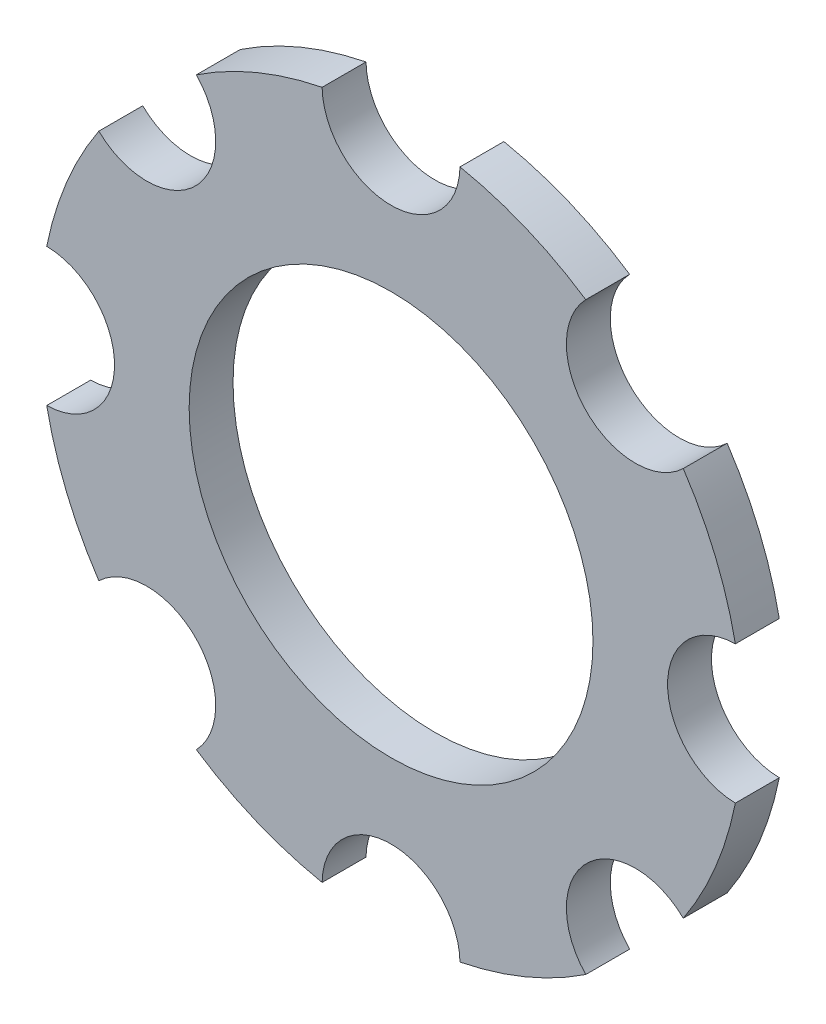
SolidWorks part; units mm, degrees
ref_plane "Front" through (0, 0, 0) normal (0, 0, 1) x (1, 0, 0)
ref_plane "Top" through (0, 0, 0) normal (0, 1, 0) x (1, 0, 0)
ref_plane "Right" through (0, 0, 0) normal (1, 0, 0) x (0, 0, -1)
sketch "Sketch1" plane through (0, 0, 0) normal (0, 0, 1) x (1, 0, 0)
  circle A0 centre (0, 0) radius 4
  circle A1 centre (0, 0) radius 2.3
extrude "Base-Extrude" add sketch "Sketch1" against normal blind 0.5
sketch "Sketch2" plane through (-3.1363, -2.0725, 0) normal (0, 0, 1) x (1, 0, 0)
  line L0 (3.1363, 2.0725) -> (11.1363, 2.0725) construction
  line L1 (3.1363, 2.0725) -> (3.1363, 3.9121) construction
  line L2 (2.3509, 16.0079) -> (2.3509, 6.0079)
  line L3 (3.9217, 6.0079) -> (3.9217, 16.0079)
  line L4 (3.9217, 16.0079) -> (2.3509, 16.0079)
  circle A0 centre (3.1363, 2.0725) radius 3.15 construction
  circle A1 centre (3.1363, 2.0725) radius 4 construction
  arc A2 (3.9217, 6.0079) -> (2.3509, 6.0079) centre (3.1363, 6.0079) cw
  dimension "D2" = 6.3
  dimension "D1" = 8
  dimension "D3" = 1.5708
  dimension "D4" = 10
extrude "TypeASlot" cut sketch "Sketch2" against normal through all
pattern_circular "TypeAPattern" count 8 over 360 about axis through (0, 0, -0.5) along (0, 0, 1) of "TypeASlot"
equation "\"D2@Sketch2\" =  ( \"D0@Sketch1\" + \"d@Sketch1\" )  / 2"
equation "\"D3@Sketch2\" = \"D0@Sketch1\" * 3.14159 / \"D1@Sketch2\" / 2"
